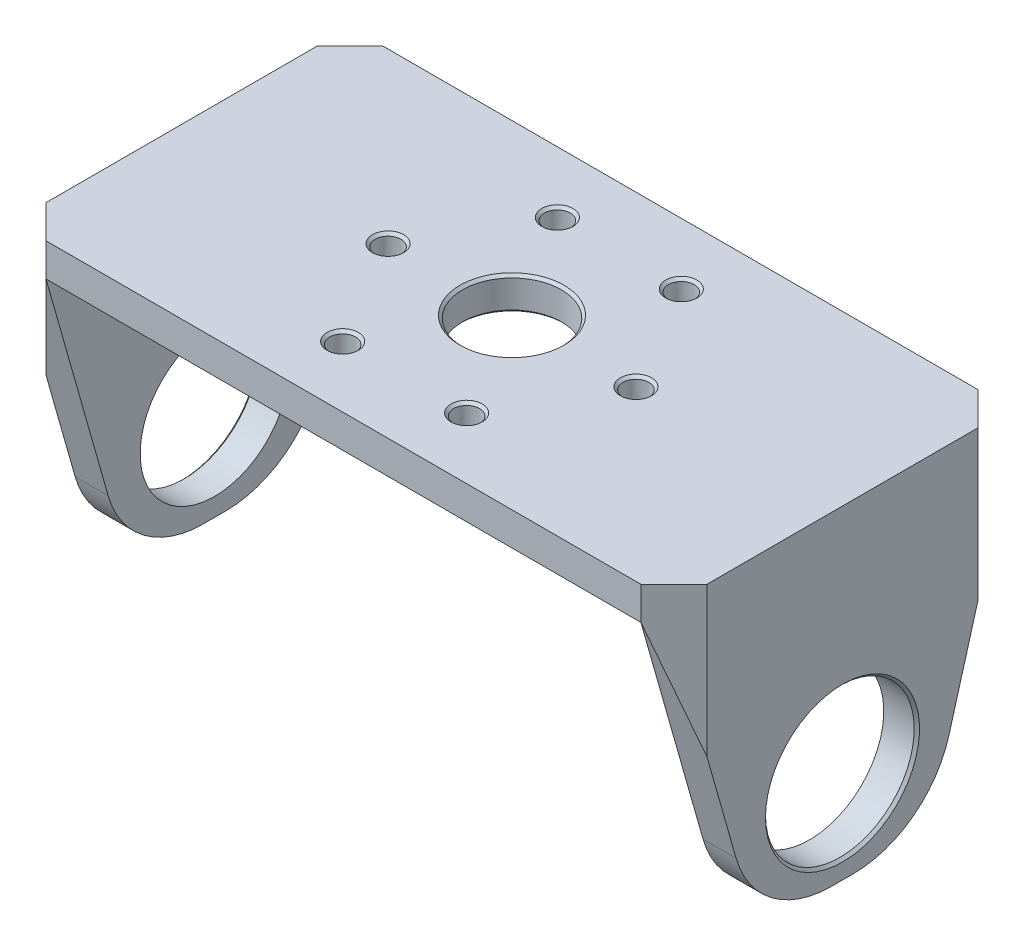
SolidWorks part; units mm, degrees
ref_plane "Front" through (0, 0, 0) normal (0, 0, 1) x (1, 0, 0)
ref_plane "Top" through (0, 0, 0) normal (0, 1, 0) x (1, 0, 0)
ref_plane "Right" through (0, 0, 0) normal (1, 0, 0) x (0, 0, -1)
ref_plane "Plane1" through (0, 6.35, 0) normal (0, 1, 0) x (1, 0, 0)
sketch "Sketch1" plane through (0, 6.35, 0) normal (0, 1, 0) x (1, 0, 0)
  line L0 (-57.15, -32.385) -> (57.15, -32.385)
  line L1 (57.15, -32.385) -> (57.15, 32.385)
  line L2 (57.15, 32.385) -> (-57.15, 32.385)
  line L3 (-57.15, 32.385) -> (-57.15, -32.385)
extrude "Boss-Extrude1" add sketch "Sketch1" against normal blind 6.35
sketch "Sketch2" plane through (57.15, 0, 0) normal (1, 0, 0) x (0, 0, -1)
  line L0 (-32.385, 6.35) -> (32.385, 6.35)
  line L1 (32.385, 6.35) -> (32.385, 0)
  line L2 (32.385, 0) -> (16.51, -55.88)
  line L3 (16.51, -55.88) -> (-16.51, -55.88)
  line L4 (-16.51, -55.88) -> (-32.385, 0)
  line L5 (-32.385, 0) -> (-32.385, 6.35)
extrude "Boss-Extrude2" add sketch "Sketch2" along normal blind 6.35
sketch "Sketch3" plane through (-57.15, 0, 0) normal (-1, 0, 0) x (0, 0, 1)
  line L0 (32.385, 0) -> (16.51, -55.88)
  line L1 (16.51, -55.88) -> (-16.51, -55.88)
  line L2 (-16.51, -55.88) -> (-32.385, 0)
  line L3 (-32.385, 0) -> (-32.385, 6.35)
  line L4 (-32.385, 6.35) -> (32.385, 6.35)
  line L5 (32.385, 6.35) -> (32.385, 0)
extrude "Boss-Extrude3" add sketch "Sketch3" along normal blind 6.35
hole_wizard "Hole1" positions "Sketch5" profile "Sketch4" legacy
sketch "Sketch5" plane through (0, 0, 0) normal (0, -1, 0) x (-1, 0, 0)
  point P0 (0, 0)
sketch "Sketch4" plane through (0, 0, 0) normal (1, 0, 0) x (0, 0, -1)
  line L0 (0, 0) -> (0, 6.35)
  line L1 (0, 6.35) -> (9.4869, 6.35)
  line L2 (9.4869, 6.35) -> (9.4869, 0)
  line L3 (9.4869, 0) -> (0, 0)
  line L4 (0, 110) -> (0, -10) construction
  dimension "Diameter" = 18.9738
  dimension "Depth" = 6.35
hole_wizard "#9 (0.196) Diameter Hole1" positions "Sketch7" profile "Sketch6" hole size "#9" standard "ANSI Inch"
sketch "Sketch7" plane through (0, 6.35, 0) normal (0, 1, 0) x (1, 0, 0)
  point P0 (11.9062, 20.6222)
sketch "Sketch6" plane through (11.9062, 6.35, -20.6222) normal (1, 0, 0) x (0, 0, 1)
  line L0 (0, 0) -> (0, 62.23)
  line L1 (0, 62.23) -> (2.4892, 62.23)
  line L2 (2.4892, 62.23) -> (2.4892, 0)
  line L5 (2.4892, 0) -> (0, 0)
  line L11 (0, -6.35) -> (0, 107.95) construction
  dimension "Thru Hole Dia." = 4.9784
  dimension "Thru Hole Depth" = 62.23
hole_wizard "#9 (0.196) Diameter Hole2" positions "Sketch9" profile "Sketch8" hole size "#9" standard "ANSI Inch"
sketch "Sketch9" plane through (0, 0, 0) normal (0, -1, 0) x (-1, 0, 0)
  point P0 (-23.8125, 0)
  point P1 (-11.9062, -20.6222)
  point P2 (11.9062, -20.6222)
  point P3 (23.8125, 0)
  point P4 (11.9062, 20.6222)
sketch "Sketch8" plane through (23.8125, 0, 0) normal (1, 0, 0) x (0, 0, -1)
  line L0 (0, 0) -> (0, 6.35)
  line L1 (0, 6.35) -> (2.4892, 6.35)
  line L2 (2.4892, 6.35) -> (2.4892, 0)
  line L5 (2.4892, 0) -> (0, 0)
  line L11 (0, -6.35) -> (0, 107.95) construction
  dimension "Thru Hole Dia." = 4.9784
  dimension "Thru Hole Depth" = 6.35
hole_wizard "Hole2" positions "Sketch11" profile "Sketch10" legacy
sketch "Sketch11" plane through (-63.5, 0, 0) normal (-1, 0, 0) x (0, 0, 1)
  point P0 (0, -38.1)
sketch "Sketch10" plane through (-63.5, -38.1, 0) normal (0, 1, 0) x (0, 0, 1)
  line L0 (0, 0) -> (0, 6.35)
  line L1 (0, 6.35) -> (14.2875, 6.35)
  line L2 (14.2875, 6.35) -> (14.2875, 0)
  line L3 (14.2875, 0) -> (0, 0)
  line L4 (0, 110) -> (0, -10) construction
  dimension "Diameter" = 28.575
  dimension "Depth" = 6.35
hole_wizard "Hole3" positions "Sketch13" profile "Sketch12" legacy
sketch "Sketch13" plane through (63.5, 0, 0) normal (1, 0, 0) x (0, 0, -1)
  point P0 (0, -38.1)
sketch "Sketch12" plane through (63.5, -38.1, 0) normal (0, 1, 0) x (0, 0, -1)
  line L0 (0, 0) -> (0, 127)
  line L1 (0, 127) -> (14.2875, 127)
  line L2 (14.2875, 127) -> (14.2875, 0)
  line L3 (14.2875, 0) -> (0, 0)
  line L4 (0, 110) -> (0, -10) construction
  dimension "Diameter" = 28.575
  dimension "Depth" = 127
chamfer "Chamfer1" distance 6.35 angle 45 4 edges at (63.5, 3.175, -32.385) (63.5, 3.175, 32.385) (-63.5, 3.175, -32.385) (-63.5, 3.175, 32.385)
chamfer "Chamfer2" distance 0.508 angle 45 16 edges at (0, 6.35, -9.4869) (-11.9062, 6.35, 18.133) (23.8125, 6.35, -2.4892) (11.9062, 0, -18.133) (-11.9062, 6.35, -23.1114) (0, 0, -9.4869) (-11.9062, 0, -23.1114) (63.5, -38.1, -14.2875) (11.9062, 6.35, 18.133) (-63.5, -38.1, 14.2875) (-23.8125, 6.35, -2.4892) (11.9062, 6.35, -18.133) (11.9062, 0, 18.133) (-23.8125, 0, -2.4892) (-11.9062, 0, 18.133) (23.8125, 0, -2.4892)
fillet "Fillet1" radius 19.05 4 edges at (60.325, -55.88, 16.51) (-60.325, -55.88, 16.51) (60.325, -55.88, -16.51) (-60.325, -55.88, -16.51) tangent propagation no
